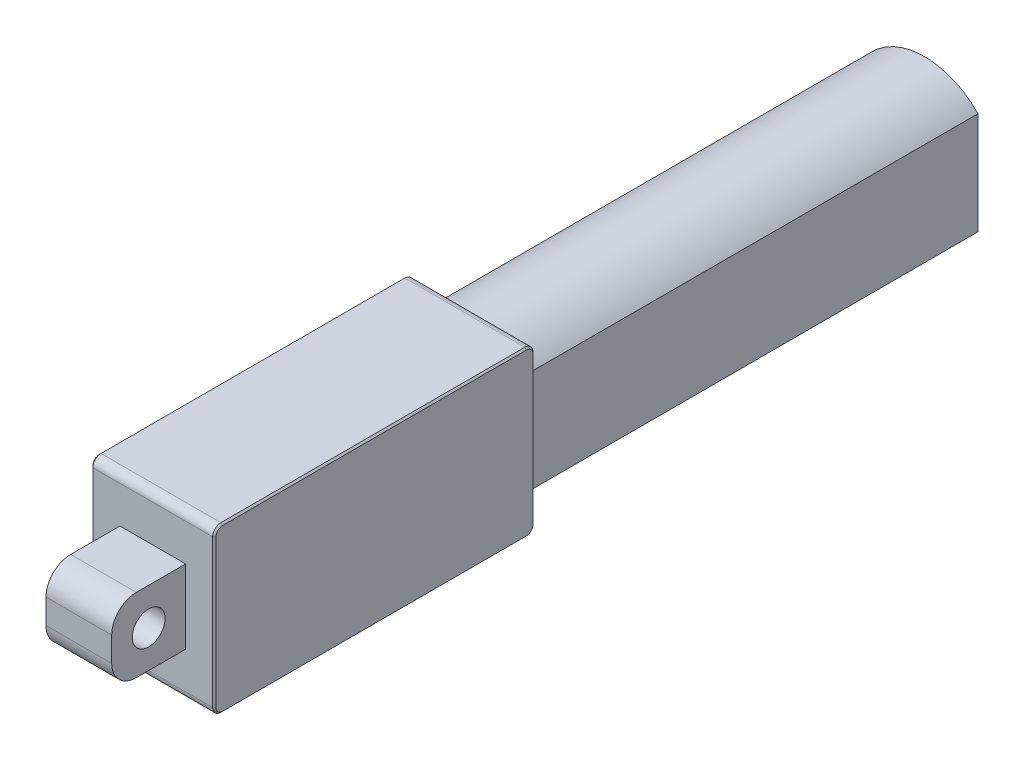
SolidWorks part; units mm, degrees
material "1350 合金"
ref_plane "前视基准面" through (0, 0, 0) normal (0, 0, 1) x (1, 0, 0)
ref_plane "上视基准面" through (0, 0, 0) normal (0, 1, 0) x (1, 0, 0)
ref_plane "右视基准面" through (0, 0, 0) normal (1, 0, 0) x (0, 0, -1)
sketch "草图1" plane through (0, 0, 0) normal (1, 0, 0) x (0, 0, -1)
  line L0 (0, 0) -> (0, 4.5) construction
  line L1 (0, 4.5) -> (4.5, 4.5)
  line L2 (4.5, 4.5) -> (4.5, -4.5)
  line L3 (4.5, -4.5) -> (-1.5, -4.5)
  line L4 (-4.5, -1.5) -> (-4.5, 1.5)
  line L5 (-1.5, 4.5) -> (0, 4.5)
  circle A0 centre (0, 0) radius 2
  arc A1 (-1.5, -4.5) -> (-4.5, -1.5) centre (-1.5, -1.5) cw
  arc A2 (-4.5, 1.5) -> (-1.5, 4.5) centre (-1.5, 1.5) cw
  point P10 (-4.5, -4.5)
  dimension "D1" = 4
  dimension "D6" = 3
  dimension "D2" = 4.5
  dimension "D3" = 4.5
  dimension "D4" = 9
  dimension "D5" = 9
extrude "凸台-拉伸1" add sketch "草图1" along normal blind 8
sketch "草图2" plane through (0, 0, -4.5) normal (0, 0, -1) x (-1, 0, 0)
  line L0 (-4, 4.5) -> (-4, -5.028) construction
  line L1 (-8, 4.5) -> (0, 4.5) construction
  line L2 (-8, 0) -> (3.818, 0) construction
  line L3 (-8, -4.5) -> (-8, 4.5) construction
  line L4 (-4, 4.5) -> (-4, 10) construction
  line L5 (-4, 10) -> (3.5, 10)
  line L6 (3.5, 10) -> (3.5, -10)
  line L7 (3.5, -10) -> (-11.5, -10)
  line L8 (-11.5, -10) -> (-11.5, 10)
  line L9 (-11.5, 10) -> (-4, 10)
  dimension "D1" = 5.5
  dimension "D2" = 7.5
  dimension "D3" = 20
  dimension "D4" = 15
extrude "凸台-拉伸2" add sketch "草图2" along normal blind 39
sketch "草图3" plane through (0, 0, -43.5) normal (0, 0, -1) x (-1, 0, 0)
  line L0 (-11.5, 10) -> (3.5, -10) construction
  line L1 (3.5, 10) -> (-11.5, -10) construction
  line L2 (-4, 10) -> (-4, -10.7224) construction
  line L3 (3.5, 10) -> (-11.5, 10) construction
  line L4 (2.5, 6.2249) -> (2.5, -6.2249)
  line L6 (-10.5, 6.2249) -> (-10.5, -6.2249)
  arc A0 (2.5, 6.2249) -> (-10.5, 6.2249) centre (-4, 0) ccw
  arc A1 (-10.5, -6.2249) -> (2.5, -6.2249) centre (-4, 0) ccw
  point P14 (-10.5, 10)
  point P15 (-10.5, -10.7224)
  point P16 (2.5, 10)
  point P17 (2.5, -10.7224)
  dimension "D1" = 18
  dimension "D2" = 6.5
  dimension "D3" = 6.5
extrude "凸台-拉伸3" add sketch "草图3" along normal blind 55
sketch "草图4" plane through (0, 0, -98.5) normal (0, 0, -1) x (-1, 0, 0)
  circle A0 centre (-4, 0) radius 4.5
  dimension "D1" = 9
extrude "切除-拉伸1" cut sketch "草图4" against normal blind 55
fillet "圆角1" radius 1 4 edges at (4, -10, -4.5) (4, -10, -43.5) (4, 10, -43.5) (4, 10, -4.5)
chamfer "倒角1" distance 0.2 angle 45 16 edges at (-3.5, -10, -24) (-3.5, -9.7071, -43.2071) (-3.5, -9.7071, -4.7929) (-3.5, 0, -43.5) (-3.5, 0, -4.5) (-3.5, 9.7071, -43.2071) (-3.5, 9.7071, -4.7929) (-3.5, 10, -24) (11.5, -10, -24) (11.5, -9.7071, -43.2071) (11.5, -9.7071, -4.7929) (11.5, 0, -43.5) (11.5, 0, -4.5) (11.5, 9.7071, -43.2071) (11.5, 9.7071, -4.7929) (11.5, 10, -24)
